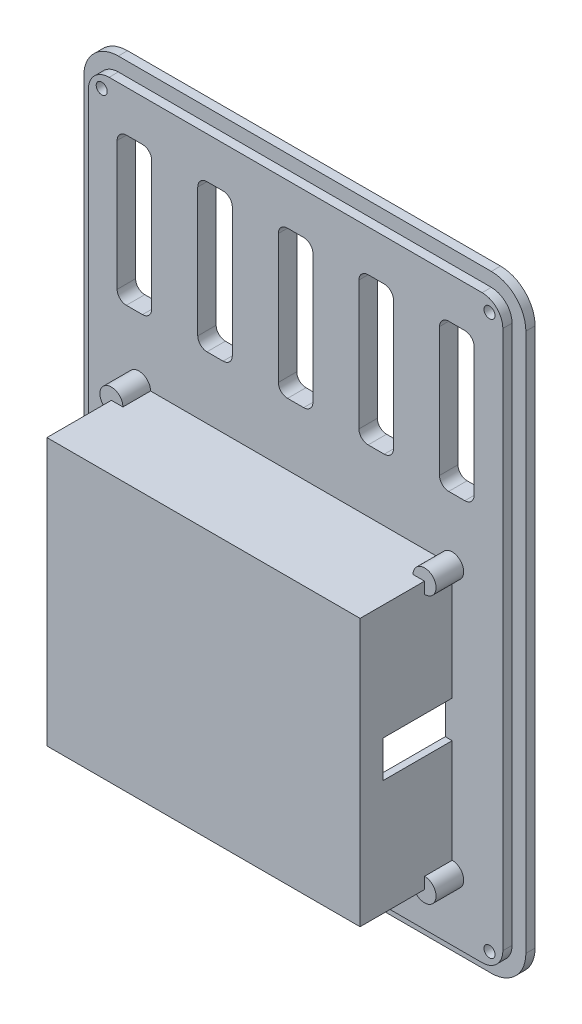
SolidWorks part; units mm, degrees
ref_plane "Front Plane" through (0, 0, 0) normal (0, 0, 1) x (1, 0, 0)
ref_plane "Top Plane" through (0, 0, 0) normal (0, 1, 0) x (1, 0, 0)
ref_plane "Right Plane" through (0, 0, 0) normal (1, 0, 0) x (0, 0, -1)
sketch "Sketch2" plane through (0, 0, 0) normal (0, 0, 1) x (1, 0, 0)
  line L20 (45, -58.5) -> (45, 58.5)
  line L21 (-40.5, -63) -> (40.5, -63)
  line L22 (-45, 58.5) -> (-45, -58.5)
  line L23 (40.5, 63) -> (-40.5, 63)
  line L24 (45, -58.5) -> (45, 58.5)
  line L25 (-40.5, -63) -> (40.5, -63)
  line L26 (-45, 58.5) -> (-45, -58.5)
  line L27 (40.5, 63) -> (-40.5, 63)
  arc A24 (40.5, -63) -> (45, -58.5) centre (40.5, -58.5) ccw
  arc A25 (-45, -58.5) -> (-40.5, -63) centre (-40.5, -58.5) ccw
  arc A26 (-40.5, 63) -> (-45, 58.5) centre (-40.5, 58.5) ccw
  arc A27 (45, 58.5) -> (40.5, 63) centre (40.5, 58.5) ccw
  arc A28 (40.5, -63) -> (45, -58.5) centre (40.5, -58.5) ccw
  arc A29 (-45, -58.5) -> (-40.5, -63) centre (-40.5, -58.5) ccw
  arc A30 (-40.5, 63) -> (-45, 58.5) centre (-40.5, 58.5) ccw
  arc A31 (45, 58.5) -> (40.5, 63) centre (40.5, 58.5) ccw
  dimension "D1" = 3
extrude "Boss-Extrude1" add sketch "Sketch2" along normal blind 2
sketch "Sketch3" plane through (0, 0, 0) normal (0, 0, -1) x (-1, 0, 0)
  line L8 (-40.5, -66) -> (40.5, -66)
  line L9 (48, -58.5) -> (48, 58.5)
  line L10 (40.5, 66) -> (-40.5, 66)
  line L11 (-48, 58.5) -> (-48, -58.5)
  line L12 (-40.5, -66) -> (40.5, -66)
  line L13 (48, -58.5) -> (48, 58.5)
  line L14 (40.5, 66) -> (-40.5, 66)
  line L15 (-48, 58.5) -> (-48, -58.5)
  arc A8 (-48, -58.5) -> (-40.5, -66) centre (-40.5, -58.5) ccw
  arc A9 (40.5, -66) -> (48, -58.5) centre (40.5, -58.5) ccw
  arc A10 (48, 58.5) -> (40.5, 66) centre (40.5, 58.5) ccw
  arc A11 (-40.5, 66) -> (-48, 58.5) centre (-40.5, 58.5) ccw
  arc A12 (-48, -58.5) -> (-40.5, -66) centre (-40.5, -58.5) ccw
  arc A13 (40.5, -66) -> (48, -58.5) centre (40.5, -58.5) ccw
  arc A14 (48, 58.5) -> (40.5, 66) centre (40.5, 58.5) ccw
  arc A15 (-40.5, 66) -> (-48, 58.5) centre (-40.5, 58.5) ccw
  dimension "D1" = 3
extrude "Boss-Extrude2" add sketch "Sketch3" along normal blind 2
sketch "Sketch5" plane through (0, 0, -2) normal (0, 0, -1) x (-1, 0, 0)
  line L0 (-48, 38) -> (48, 38) construction
  line L1 (-36.75, 22) -> (-33.25, 22)
  line L2 (-38.75, 24) -> (-38.75, 52)
  line L3 (-36.75, 54) -> (-33.25, 54)
  line L4 (-31.25, 24) -> (-31.25, 52)
  line L5 (-38.75, 22) -> (-31.25, 54) construction
  line L6 (-38.75, 54) -> (-31.25, 22) construction
  line L7 (-48, 58.5) -> (-48, -58.5) construction
  line L8 (48, -58.5) -> (48, 58.5) construction
  line L9 (40.5, 66) -> (-40.5, 66) construction
  line L10 (-21.25, 24) -> (-21.25, 52)
  line L11 (-13.75, 24) -> (-13.75, 52)
  line L12 (-19.25, 54) -> (-15.75, 54)
  line L13 (-19.25, 22) -> (-15.75, 22)
  line L14 (-21.25, 54) -> (-13.75, 22) construction
  line L15 (-21.25, 22) -> (-13.75, 54) construction
  line L16 (-3.75, 24) -> (-3.75, 52)
  line L17 (3.75, 24) -> (3.75, 52)
  line L18 (-1.75, 54) -> (1.75, 54)
  line L19 (-1.75, 22) -> (1.75, 22)
  line L20 (-3.75, 54) -> (3.75, 22) construction
  line L21 (-3.75, 22) -> (3.75, 54) construction
  line L22 (13.75, 24) -> (13.75, 52)
  line L23 (21.25, 24) -> (21.25, 52)
  line L24 (15.75, 54) -> (19.25, 54)
  line L25 (15.75, 22) -> (19.25, 22)
  line L26 (13.75, 54) -> (21.25, 22) construction
  line L27 (13.75, 22) -> (21.25, 54) construction
  line L28 (31.25, 24) -> (31.25, 52)
  line L29 (38.75, 24) -> (38.75, 52)
  line L30 (33.25, 54) -> (36.75, 54)
  line L31 (33.25, 22) -> (36.75, 22)
  line L32 (31.25, 54) -> (38.75, 22) construction
  line L33 (31.25, 22) -> (38.75, 54) construction
  line L34 (-3.5, 66) -> (-3.5, 34) construction
  arc A0 (31.25, 52) -> (33.25, 54) centre (33.25, 52) cw
  arc A1 (38.75, 52) -> (36.75, 54) centre (36.75, 52) ccw
  arc A2 (38.75, 24) -> (36.75, 22) centre (36.75, 24) cw
  arc A3 (31.25, 24) -> (33.25, 22) centre (33.25, 24) ccw
  arc A4 (13.75, 24) -> (15.75, 22) centre (15.75, 24) ccw
  arc A5 (21.25, 24) -> (19.25, 22) centre (19.25, 24) cw
  arc A6 (21.25, 52) -> (19.25, 54) centre (19.25, 52) ccw
  arc A7 (13.75, 52) -> (15.75, 54) centre (15.75, 52) cw
  arc A8 (3.75, 24) -> (1.75, 22) centre (1.75, 24) cw
  arc A9 (-3.75, 24) -> (-1.75, 22) centre (-1.75, 24) ccw
  arc A10 (3.75, 52) -> (1.75, 54) centre (1.75, 52) ccw
  arc A11 (-3.75, 52) -> (-1.75, 54) centre (-1.75, 52) cw
  arc A12 (-21.25, 24) -> (-19.25, 22) centre (-19.25, 24) ccw
  arc A13 (-13.75, 24) -> (-15.75, 22) centre (-15.75, 24) cw
  arc A14 (-13.75, 52) -> (-15.75, 54) centre (-15.75, 52) ccw
  arc A15 (-21.25, 52) -> (-19.25, 54) centre (-19.25, 52) cw
  arc A16 (-33.25, 22) -> (-31.25, 24) centre (-33.25, 24) ccw
  arc A17 (-36.75, 22) -> (-38.75, 24) centre (-36.75, 24) cw
  arc A18 (-33.25, 54) -> (-31.25, 52) centre (-33.25, 52) cw
  arc A19 (-38.75, 52) -> (-36.75, 54) centre (-36.75, 52) cw
  point P0 (-35, 38)
  point P13 (-17.5, 38)
  point P19 (0, 38)
  point P24 (17.5, 38)
  point P29 (35, 38)
  dimension "D6" = 2
  dimension "D1" = 7.5
  dimension "D2" = 32
  dimension "D3" = 28
  dimension "D5" = 10
  dimension "D4" = 5
extrude "Cut-Extrude1" cut sketch "Sketch5" against normal through all
hole_wizard "CBORE for M2 Pan Head Machine Screw1" positions "Sketch7" profile "Sketch6" counterbore size "M2" standard "ANSI Metric" end condition through all
sketch "Sketch7" plane through (0, 0, -2) normal (0, 0, -1) x (-1, 0, 0)
  point P0 (-42.1, 60.1)
  point P3 (42.1, 60.1)
  point P6 (-42.1, -60.1)
  point P9 (42.1, -60.1)
sketch "Sketch6" plane through (42.1, 60.1, -2) normal (1, 0, 0) x (0, 1, 0)
  line L0 (0, 0) -> (0, 4)
  line L1 (0, 4) -> (1.2, 4)
  line L3 (1.2, 4) -> (1.2, 1.6)
  line L4 (1.2, 1.6) -> (2.5, 1.6)
  line L5 (2.5, 1.6) -> (2.5, 0)
  line L7 (2.5, 0) -> (0, 0)
  line L11 (0, -6.35) -> (0, 107.95) construction
  dimension "Thru Hole Dia." = 2.4
  dimension "Thru Hole Depth" = 4
  dimension "C'Bore Dia." = 5
  dimension "C'Bore Depth" = 1.6
sketch "Sketch8" plane through (0, 0, -2) normal (0, 0, -1) x (-1, 0, 0)
  line L0 (0, 66) -> (0, -66) construction
  line L1 (-32.5, 7) -> (32.5, 7)
  line L2 (-32.5, 7) -> (-32.5, -48)
  line L3 (-32.5, -48) -> (32.5, -48)
  line L4 (32.5, 7) -> (32.5, -48)
  line L5 (-32.5, 7) -> (32.5, -48) construction
  line L6 (-32.5, -48) -> (32.5, 7) construction
  line L7 (40.5, 66) -> (-40.5, 66) construction
  line L8 (-40.5, -66) -> (40.5, -66) construction
  line L9 (-34, 8.5) -> (34, 8.5)
  line L10 (34, 8.5) -> (34, -49.5)
  line L11 (-34, -49.5) -> (34, -49.5)
  line L12 (-34, 8.5) -> (-34, -49.5)
  point P0 (0, -20.5)
  dimension "D1" = 18
  dimension "D2" = 55
  dimension "D3" = 65
  dimension "D4" = 1.5
extrude "Boss-Extrude3" add sketch "Sketch8<3>" against normal blind 20 from surface contours L9 L10 L11 L12 starting at face at (40.9, 60.1, 2)
sketch "Sketch8<3>" plane through (0, 0, -2) normal (0, 0, -1) x (-1, 0, 0) same geometry as "Sketch8"
extrude "Cut-Extrude2" cut sketch "Sketch8" against normal blind 22 contours L1 L4 L3 L2
sketch "Sketch9" plane through (0, 0, -2) normal (0, 0, -1) x (-1, 0, 0)
  line L18 (-36.5, -52) -> (36.5, -52)
  line L19 (36.5, -52) -> (36.5, 11)
  line L20 (-36.5, 11) -> (-36.5, -52)
  line L21 (36.5, 11) -> (-36.5, 11)
  line L22 (-36.5, -52) -> (36.5, -52)
  line L23 (36.5, -52) -> (36.5, 11)
  line L24 (-36.5, 11) -> (-36.5, -52)
  line L25 (36.5, 11) -> (-36.5, 11)
  dimension "D1" = 4
extrude "Cut-Extrude3" cut sketch "Sketch9" against normal blind 2
sketch "Sketch10" plane through (0, 0, 2) normal (0, 0, 1) x (1, 0, 0)
  line L0 (32.5, 7) -> (32, 7)
  line L1 (-32.5, 7) -> (-32.5, 6.5)
  line L2 (-32.5, -48) -> (-32, -48)
  line L3 (32.5, -48) -> (32.5, -47.5)
  line L4 (32.5, 6.5) -> (32.5, 7)
  line L5 (-32, 7) -> (-32.5, 7)
  line L6 (-32.5, -47.5) -> (-32.5, -48)
  line L7 (32, -48) -> (32.5, -48)
  arc A0 (32.5, 6.5) -> (32, 7) centre (34, 8.5) ccw
  arc A1 (-32, 7) -> (-32.5, 6.5) centre (-34, 8.5) ccw
  arc A2 (-32.5, -47.5) -> (-32, -48) centre (-34, -49.5) ccw
  arc A3 (32, -48) -> (32.5, -47.5) centre (34, -49.5) ccw
  dimension "D1" = 5
extrude "Boss-Extrude4" add sketch "Sketch10" along normal blind 6
hole_wizard "CSK for M2 Flat Head Machine Screw2" positions "Sketch14" profile "Sketch13" countersink size "M2" standard "ANSI Metric"
sketch "Sketch14" plane through (0, 0, 0) normal (0, 0, -1) x (-1, 0, 0)
  point P0 (-34, 8.5)
  point P3 (34, 8.5)
  point P6 (-34, -49.5)
  point P9 (34, -49.5)
sketch "Sketch13" plane through (34, 8.5, 0) normal (1, 0, 0) x (0, 1, 0)
  line L0 (0, 0) -> (0, 6.9013)
  line L1 (0, 6.9013) -> (1.5, 6)
  line L2 (1.5, 6) -> (1.5, 0.5038)
  line L3 (1.5, 0.5038) -> (1.635, 0)
  line L5 (1.635, 0) -> (0, 0)
  line L6 (-1.5, 0.5038) -> (-1.635, 0) construction
  line L10 (0, 6.9013) -> (-1.5, 6) construction
  line L11 (0, -6.35) -> (0, 107.95) construction
  dimension "Hole Dia." = 3
  dimension "Hole Depth" = 6
  dimension "Near C'Sink Dia." = 3.27
  dimension "Near C'Sink Angle" = 30
  dimension "Drill Angle" = 118
sketch "Sketch15" plane through (34, 0, 0) normal (1, 0, 0) x (0, 0, -1)
  line L1 (-17, -16.5) -> (-2, -16.5)
  line L2 (-17, -16.5) -> (-17, -24.5)
  line L3 (-17, -24.5) -> (-2, -24.5)
  line L4 (-2, -16.5) -> (-2, -24.5)
  line L5 (-2, -58.5) -> (-2, 58.5) construction
  line L6 (-22, -20.5) -> (2, -20.5) construction
  line L7 (-22, -49.5) -> (-22, 8.5) construction
  line L8 (2, 58.5) -> (2, -58.5) construction
  point P12 (-17, -20.5)
  dimension "D1" = 8
  dimension "D2" = 15
extrude "Cut-Extrude4" cut sketch "Sketch15" against normal through all
sketch "Sketch16" plane through (0, 0, -2) normal (0, 0, -1) x (-1, 0, 0)
  line L0 (2.5158, -57.4) -> (-2.5158, -57.4)
  line L1 (-4, -54.9) -> (-4, -55.719)
  line L2 (3.5, -54.4) -> (-3.5, -54.4)
  line L3 (4, -54.9) -> (4, -55.719)
  line L4 (0, -54.4) -> (0, -57.4) construction
  line L5 (-3.8841, -56.0391) -> (-2.8999, -57.2201)
  line L6 (3.8841, -56.0391) -> (2.8999, -57.2201)
  line L7 (0, 66) -> (0, -66) construction
  line L8 (40.5, 66) -> (-40.5, 66) construction
  line L9 (-40.5, -66) -> (40.5, -66) construction
  line L10 (40.5, -63) -> (-40.5, -63) construction
  arc A0 (-4, -55.719) -> (-3.8841, -56.0391) centre (-3.5, -55.719) ccw
  arc A1 (-2.5158, -57.4) -> (-2.8999, -57.2201) centre (-2.5158, -56.9) cw
  arc A2 (2.5158, -57.4) -> (2.8999, -57.2201) centre (2.5158, -56.9) ccw
  arc A3 (4, -55.719) -> (3.8841, -56.0391) centre (3.5, -55.719) cw
  arc A4 (4, -54.9) -> (3.5, -54.4) centre (3.5, -54.9) ccw
  arc A5 (-3.5, -54.4) -> (-4, -54.9) centre (-3.5, -54.9) ccw
  point P7 (0, -55.9)
  point P19 (-4, -55.9)
  point P22 (-2.75, -57.4)
  point P25 (2.75, -57.4)
  point P30 (4, -54.4)
  point P33 (-4, -54.4)
  dimension "D6" = 0.5
  dimension "D1" = 8
  dimension "D2" = 5.5
  dimension "D3" = 3
  dimension "D4" = 1.5
  dimension "D5" = 5.6
extrude "Cut-Extrude5" cut sketch "Sketch16" against normal through all
